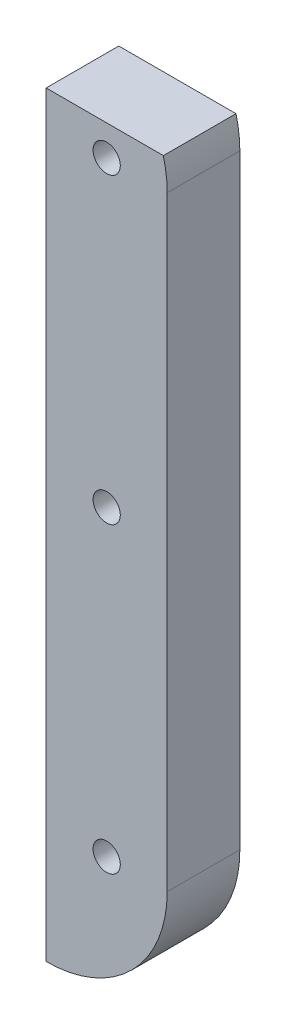
SolidWorks part; units mm, degrees
ref_plane "前视基准面" through (0, 0, 0) normal (0, 0, 1) x (1, 0, 0)
ref_plane "上视基准面" through (0, 0, 0) normal (0, 1, 0) x (1, 0, 0)
ref_plane "右视基准面" through (0, 0, 0) normal (1, 0, 0) x (0, 0, -1)
sketch "草图1" plane through (0, 0, 0) normal (0, 0, 1) x (1, 0, 0)
  line L1 (-10, 70) -> (10, 70)
  line L2 (-10, 70) -> (-10, -70)
  line L3 (-10, -70) -> (10, -70)
  line L4 (10, 70) -> (10, -70)
  line L5 (-10, 70) -> (10, -70) construction
  line L6 (-10, -70) -> (10, 70) construction
  circle A0 centre (0, -50) radius 2.25 construction
  circle A1 centre (0, 0) radius 2.25 construction
  circle A2 centre (0, 50) radius 2.25 construction
  circle A3 centre (0, -50) radius 2.25
  circle A4 centre (0, 0) radius 2.25
  circle A5 centre (0, 50) radius 2.25
  point P0 (0, 0)
  dimension "D1" = 140
  dimension "D2" = 20
extrude "凸台-拉伸1" add sketch "草图1" along normal blind 12
fillet "圆角1" radius 20 2 edges at (10, -70, 6) (10, 70, 6)
sketch "草图2" plane through (0, 0, 12) normal (0, 0, 1) x (1, 0, 0)
  line L1 (-10, 70) -> (9.3649, 70)
  line L2 (-10, 70) -> (-10, 55)
  line L3 (-10, 55) -> (9.3649, 55)
  line L4 (9.3649, 70) -> (9.3649, 55)
  arc A0 (10, 50) -> (-10, 70) centre (-10, 50) ccw construction
  circle A1 centre (0, 50) radius 2.25 construction
  dimension "D1" = 5
extrude "切除-拉伸1" cut sketch "草图2" against normal through all
